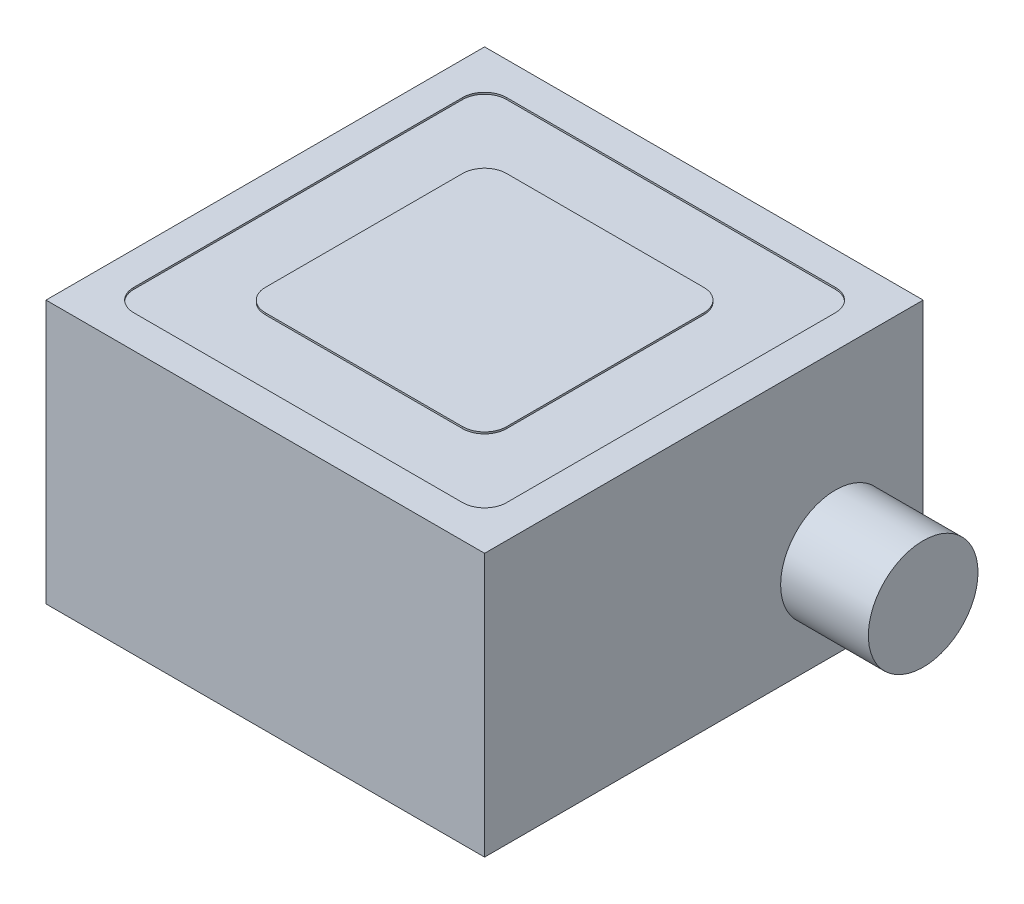
SolidWorks part; units mm, degrees
ref_plane "Front Plane" through (0, 0, 0) normal (0, 0, 1) x (1, 0, 0)
ref_plane "Top Plane" through (0, 0, 0) normal (0, 1, 0) x (1, 0, 0)
ref_plane "Right Plane" through (0, 0, 0) normal (1, 0, 0) x (0, 0, -1)
sketch "Sketch1" plane through (0, 0, 0) normal (0, 1, 0) x (1, 0, 0)
  line L1 (0, -31.75) -> (63.5, -31.75)
  line L2 (0, -31.75) -> (0, 31.75)
  line L3 (0, 31.75) -> (63.5, 31.75)
  line L4 (63.5, -31.75) -> (63.5, 31.75)
  circle A0 centre (0, 0) radius 25.4 construction
  dimension "A" = 50.8
  dimension "Wd." = 63.5
  dimension "Lg." = 63.5
extrude "Boss-Extrude1" add sketch "Sketch1" along normal blind 38.1
sketch "Sketch2" plane through (0, 38.1, 0) normal (0, 1, 0) x (1, 0, 0)
  line L0 (4.7625, 0) -> (0, 0) construction
  line L1 (17.4625, 17.4625) -> (46.0375, 17.4625)
  line L2 (14.2875, 14.2875) -> (14.2875, -14.2875)
  line L3 (17.4625, -17.4625) -> (46.0375, -17.4625)
  line L4 (49.2125, 14.2875) -> (49.2125, -14.2875)
  line L5 (7.9375, 26.9875) -> (55.5625, 26.9875)
  line L6 (4.7625, 23.8125) -> (4.7625, -23.8125)
  line L7 (7.9375, -26.9875) -> (55.5625, -26.9875)
  line L8 (58.7375, 23.8125) -> (58.7375, -23.8125)
  line L9 (4.7625, 0) -> (14.2875, 0) construction
  line L10 (14.2875, 0) -> (49.2125, 0) construction
  line L11 (49.2125, 0) -> (58.7375, 0) construction
  line L12 (58.7375, 0) -> (63.5, 0) construction
  line L13 (63.5, -31.75) -> (63.5, 31.75) construction
  line L14 (31.75, 31.75) -> (31.75, 26.9875) construction
  line L15 (63.5, 31.75) -> (0, 31.75) construction
  line L16 (31.75, 26.9875) -> (31.75, 17.4625) construction
  line L17 (31.75, 17.4625) -> (31.75, -17.4625) construction
  line L18 (31.75, -17.4625) -> (31.75, -26.9875) construction
  line L19 (31.75, -26.9875) -> (31.75, -31.75) construction
  line L20 (0, -31.75) -> (63.5, -31.75) construction
  arc A0 (46.0375, 17.4625) -> (49.2125, 14.2875) centre (46.0375, 14.2875) cw
  arc A1 (46.0375, -17.4625) -> (49.2125, -14.2875) centre (46.0375, -14.2875) ccw
  arc A2 (14.2875, -14.2875) -> (17.4625, -17.4625) centre (17.4625, -14.2875) ccw
  arc A3 (17.4625, 17.4625) -> (14.2875, 14.2875) centre (17.4625, 14.2875) ccw
  arc A4 (55.5625, 26.9875) -> (58.7375, 23.8125) centre (55.5625, 23.8125) cw
  arc A5 (55.5625, -26.9875) -> (58.7375, -23.8125) centre (55.5625, -23.8125) ccw
  arc A6 (4.7625, -23.8125) -> (7.9375, -26.9875) centre (7.9375, -23.8125) ccw
  arc A7 (7.9375, 26.9875) -> (4.7625, 23.8125) centre (7.9375, 23.8125) ccw
  dimension "D3" = 3.175
  dimension "D4" = 3.175
  dimension "D1" = 4.7625
  dimension "D2" = 9.525
extrude "Cut-Extrude0" cut sketch "Sketch2" against normal blind 0.254
sketch "Sketch3" plane through (0, 0, 0) normal (0, -1, 0) x (1, 0, 0)
  line L0 (0, 0) -> (31.75, 0) construction
  circle A0 centre (31.75, 0) radius 3.175
  circle A1 centre (31.75, 0) radius 3.175 construction
  point P3 (28.575, 0)
  point P4 (34.925, 0)
  point P5 (31.75, 0)
  point P10 (28.575, 0)
  point P11 (34.925, 0)
  dimension "Hole Dia." = 6.35
  dimension "CtoC" = 0
  dimension "L1" = 31.75
extrude "Cut-Extrude1" cut sketch "Sketch3" against normal blind 12.7
sketch "Sketch4" plane through (0, 0, 0) normal (0, -1, 0) x (1, 0, 0)
  circle A1 centre (31.75, 0) radius 3.175
  circle A2 centre (31.75, 0) radius 3.175
  point P0 (28.575, 0)
  dimension "D1" = 0
curve "Helix/Spiral1" pitch 1.27 height 13.97 turns 11 parameters "Pitch"=1.27
sketch "Sketch5" plane through (0, 0, 0) normal (0, 0, 1) x (1, 0, 0)
  line L0 (28.4375, 0.0794) -> (28.4375, -1.1906) construction
  line L1 (28.4375, -1.1906) -> (29.5374, -0.5556) construction
  line L2 (29.5374, -0.5556) -> (28.4375, 0.0794) construction
  line L3 (28.575, 0) -> (28.575, -1.1113) construction
  line L4 (29.3999, -0.4763) -> (29.3999, -0.635) construction
  line L5 (29.5374, -0.5556) -> (29.3999, -0.5556) construction
  line L6 (29.3999, -0.5556) -> (29.2624, -0.5556) construction
  line L7 (28.575, -0.5556) -> (28.4375, -0.5556) construction
  line L8 (28.5063, -1.1509) -> (28.5063, 0.0397)
  line L9 (28.5063, 0.0397) -> (29.2624, -0.3969)
  line L10 (29.2624, -0.3969) -> (29.2624, -0.7144)
  line L11 (29.2624, -0.7144) -> (28.5063, -1.1509)
  point P16 (28.5063, -0.5556)
  dimension "D1" = 1.27
  dimension "D2" = 0.1588
sketch "Sketch6" plane through (0, 0, 0) normal (0, -1, 0) x (1, 0, 0)
  circle A0 centre (31.75, 0) radius 3.3125
sweep "Sweep1" add profiles "Sketch5" path "Helix/Spiral1"
extrude "Cut-Extrude2" cut sketch "Sketch6" against normal through all draft 45 and the other way through all
sketch "Sketch7" plane through (0, 0, 0) normal (1, 0, 0) x (0, 0, -1)
  line L0 (19.05, 12.7) -> (19.05, 0) construction
  line L1 (-31.75, 38.1) -> (-31.75, 0) construction
  line L2 (-31.75, 0) -> (31.75, 0) construction
  circle A0 centre (19.05, 12.7) radius 7.9375
  dimension "Wire Dia." = 15.875
  dimension "B" = 50.8
  dimension "C" = 12.7
pattern_linear "LPattern1" [suppressed] count 2 spacing 25.4 along (1, 0, 0)
sketch "Sketch8" plane through (0, 0, 0) normal (0, 0, 1) x (1, 0, 0)
  line L0 (0, 12.7) -> (76.2, 12.7) construction
  line L2 (63.5, 38.1) -> (63.5, 0) construction
  dimension "D1" = 12.7
extrude "Boss-Extrude2" add sketch "Sketch7" against normal up to surface (12.7 mm away) from vertex at 76.2 up to face at (63.5, 19.05, 0) starting at point (76.2, 12.7, 0)
sketch "Sketch9" plane through (0, 0, 0) normal (0, 0, 1) x (1, 0, 0)
  line L0 (28.575, 0) -> (28.575, 12.7) construction
  line L1 (28.575, 12.7) -> (34.925, 12.7) construction
  line L2 (34.925, 12.7) -> (34.925, 0) construction
  line L3 (28.575, 12.7) -> (32.702, 12.7) construction
  line L4 (28.575, 0) -> (28.575, 12.7) construction
  line L5 (34.925, 0) -> (34.925, 12.7) construction
  line L6 (34.925, 12.7) -> (28.575, 12.7) construction
equation "\"D3@Helix/Spiral1\" = \"Pitch@Helix/Spiral1\" + \"Hole Depth@Cut-Extrude1\""
equation "\"D1@Sketch5\" = \"Pitch@Helix/Spiral1\""
equation "\"D2@Sketch5\" = \"D1@Sketch5\" / 8"
equation "\"D3@LPattern1\" = \"CtoC@Sketch3\""
